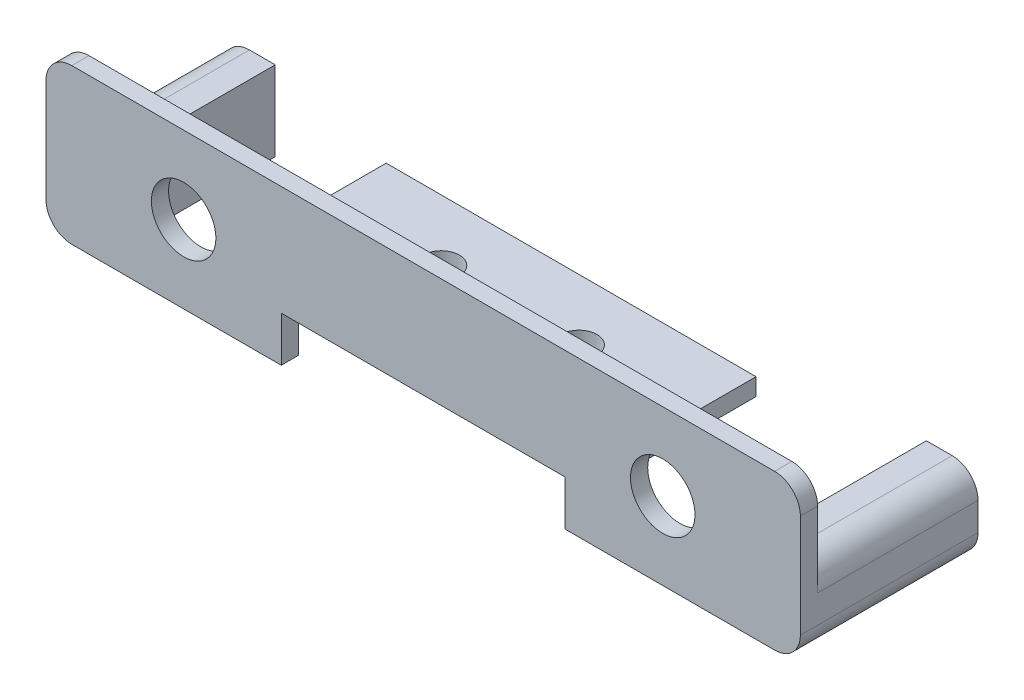
SolidWorks part; units mm, degrees
ref_plane "Front Plane" through (0, 0, 0) normal (0, 0, 1) x (1, 0, 0)
ref_plane "Top Plane" through (0, 0, 0) normal (0, 1, 0) x (1, 0, 0)
ref_plane "Right Plane" through (0, 0, 0) normal (1, 0, 0) x (0, 0, -1)
sketch "Sketch3" plane through (0, 0, 0) normal (0, 1, 0) x (1, 0, 0)
  line L1 (-21.5, 0) -> (21.5, 0)
  line L2 (-21.5, 0) -> (-21.5, 15.2)
  line L3 (-21.5, 15.2) -> (21.5, 15.2)
  line L4 (21.5, 0) -> (21.5, 15.2)
  line L5 (-8, 8.1) -> (8, 8.1) construction
  circle A0 centre (-8, 8.1) radius 2.1
  circle A1 centre (8, 8.1) radius 2.1
  point P6 (0, 0)
  point P12 (0, 8.1)
  dimension "D2" = 4.2
  dimension "D1" = 16
  dimension "D3" = 5
  dimension "D4" = 6
  dimension "D5" = 43
extrude "Boss-Extrude5" add sketch "Sketch3" against normal blind 2 separate body
sketch "Sketch1" plane through (0, 0, 0) normal (0, 0, 1) x (1, 0, 0)
  line L0 (0, -1000) -> (0, 49000) construction
  line L1 (-43.85, -9.25) -> (-16.5, -9.25)
  line L2 (-43.85, -9.25) -> (-43.85, 8.75)
  line L4 (43.85, -9.25) -> (43.85, 8.75)
  line L5 (-43.85, -0.25) -> (43.85, -0.25) construction
  line L6 (-43.85, 8.75) -> (43.85, 8.75)
  line L15 (-37.85, -24) -> (-37.85, 0) construction
  line L17 (-16.5, -9.25) -> (-16.5, -4)
  line L18 (-16.5, -4) -> (16.5, -4)
  line L19 (16.5, -4) -> (16.5, -9.25)
  line L20 (16.5, -9.25) -> (43.85, -9.25)
  line L22 (-21.5, -2) -> (21.5, -2) construction
  line L23 (-21.5, 0) -> (21.5, 0) construction
  line L24 (-21.5, -2) -> (-21.5, 0) construction
  circle A0 centre (-27.85, -0.25) radius 3.75
  circle A2 centre (27.85, -0.25) radius 3.75
  point P14 (0, -4)
  dimension "D3" = 7.5
  dimension "D4" = 10
  dimension "D1" = 18
  dimension "D2" = 6
  dimension "D5" = 5
  dimension "D6" = 2
  dimension "D7" = 4
extrude "Boss-Extrude1" add sketch "Sketch1" along normal blind 2
chamfer "Chamfer1" distance 1.5 angle 45 1 edges at (0, -2, 0)
sketch "Sketch5" plane through (0, 0, 0) normal (0, 0, -1) x (-1, 0, 0)
  line L0 (43.85, -9.25) -> (16.5, -9.25) construction
  line L1 (43.85, 0) -> (37.85, 0)
  line L2 (43.85, 0) -> (43.85, -9.25)
  line L3 (43.85, -9.25) -> (37.85, -9.25)
  line L4 (37.85, 0) -> (37.85, -9.25)
  line L5 (37.85, -24) -> (37.85, 0) construction
  line L6 (37.85, 0) -> (60.85, 0) construction
extrude "Boss-Extrude4" add sketch "Sketch5" along normal up to surface (18.65 mm away)
mirror "Mirror2" about plane through (0, 0, 0) normal (1, 0, 0) of "Boss-Extrude4"
fillet "Fillet1" radius 3 6 edges at (43.85, 8.75, 1) (-43.85, -9.25, -8.325) (-43.85, 8.75, 1) (-43.85, 0, -9.325) (43.85, 0, -9.325) (43.85, -9.25, -8.325)
equation "\"width\"= 24"
equation "\"thk\"= 3"
equation "\"holesize\"= 4.2"
equation "\"holedistance\"= ( 20 + 12 ) / 2"
equation "\"threaded_hole\"= 3.9"
equation "\"fillet_radius\"= 2"
equation "\"ground_clearance\"= 25"
equation "\"tire_thk\"= 3"
equation "\"innerwheel_diam\" = \"wheel_diam\"-2*\"tire_thk\""
equation "\"innerwheel_thk\"= 8"
equation "\"wheel_diam\"= 2*(\"width\"/2+\"ground_clearance\")"
equation "\"coloursensor_holesize\"= 2.65"
equation "\"hole_to_edge\" = 4"
equation "\"D1@Sketch3\"=\"holedistance\""
equation "\"D2@Sketch3\"=\"holesize\""
